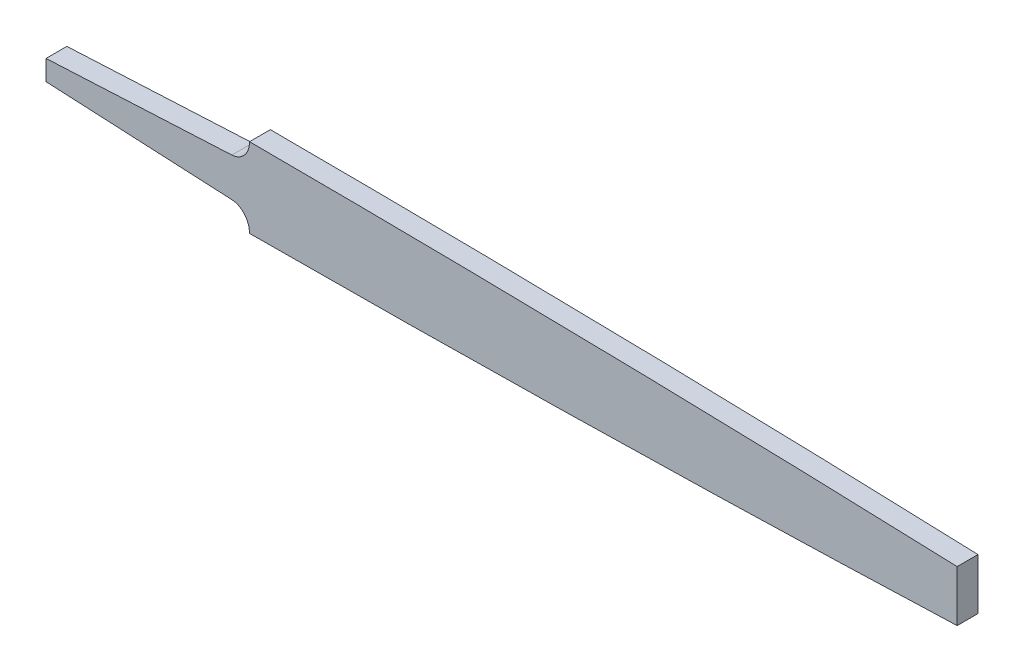
SolidWorks part; units mm, degrees
ref_plane "Front Plane" through (0, 0, 0) normal (0, 0, 1) x (1, 0, 0)
ref_plane "Top Plane" through (0, 0, 0) normal (0, 1, 0) x (1, 0, 0)
ref_plane "Right Plane" through (0, 0, 0) normal (1, 0, 0) x (0, 0, -1)
ref_axis "Axis1" through (-33.0333, 0, 0) along (1, 0, 0)
ref_axis "Axis2" through (0, 24.5224, 0) along (0, -1, 0)
ref_axis "Axis3" through (0, 0, -30.7663) along (0, 0, 1)
sketch "Sketch1" plane through (0, 0, 0) normal (0, 0, 1) x (1, 0, 0)
  line L0 (-98.5, 0) -> (98.5, 0) construction
  line L1 (-98.5, -2) -> (-98.5, 2)
  line L2 (-98.5, 2) -> (-58.3175, 3.835)
  line L3 (-54.5, 7.8308) -> (-54.5, 7.885)
  line L4 (98.5, 5.075) -> (98.5, -5.075)
  line L5 (-54.5, -7.8308) -> (-54.5, -7.885)
  line L6 (-98.5, -2) -> (-58.3175, -3.835)
  arc A0 (-54.5, -7.8308) -> (-58.3175, -3.835) centre (-58.5, -7.8308) ccw
  arc A1 (-58.3175, 3.835) -> (-54.5, 7.8308) centre (-58.5, 7.8308) ccw
  spline S0 degree 2 poles (-54.5, 7.885) (22.0289, 7.6807) (98.5, 5.075) knots 0 0 0 1 1 1
  spline S1 degree 2 poles (-54.5, -7.885) (22.0289, -7.6807) (98.5, -5.075) knots 0 0 0 1 1 1
  point P2 (0, 0)
  point P18 (-54.5, -4.0093)
  point P21 (-54.5, 4.0093)
  dimension "D6" = 4
  dimension "D1" = 197
  dimension "D2" = 2
  dimension "D3" = 44
  dimension "D4" = 7.885
  dimension "D5" = 5.075
  dimension "D7" = 3.835
extrude "Boss-Extrude1" add sketch "Sketch1" along normal blind 2.07 and the other way blind 2.07
scale "Scale1" scale about origin uniform scaling no x scale factor 1.01 y scale factor 1.1 z scale factor 1.1
